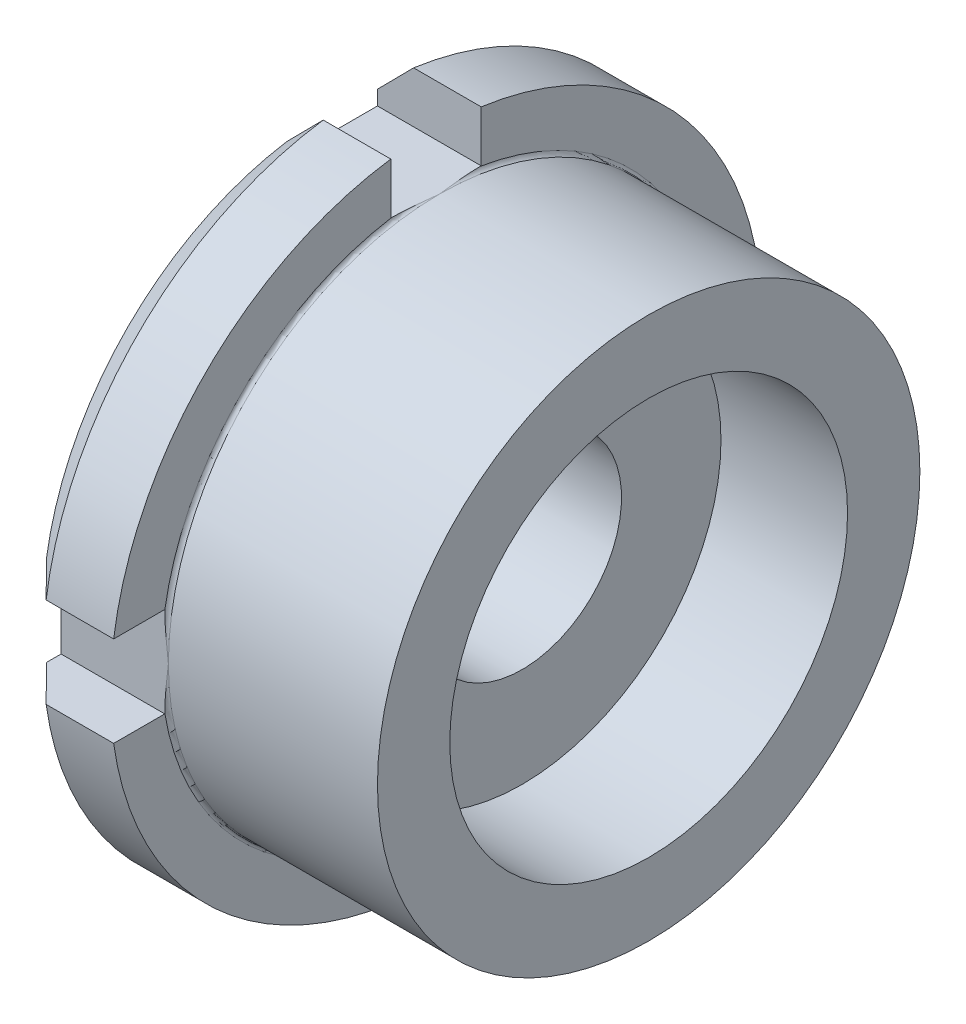
SolidWorks part; units mm, degrees
ref_plane "Front Plane" through (0, 0, 0) normal (0, 0, 1) x (1, 0, 0)
ref_plane "Top Plane" through (0, 0, 0) normal (0, 1, 0) x (1, 0, 0)
ref_plane "Right Plane" through (0, 0, 0) normal (1, 0, 0) x (0, 0, -1)
sketch "Sketch1" plane through (0, 0, 0) normal (0, 0, 1) x (1, 0, 0)
  line L0 (0, 0) -> (0, 5.5) construction
  line L1 (5.5, 5.5) -> (10.5, 5.5)
  line L2 (10.5, 5.5) -> (10.5, 11)
  line L3 (10.5, 11) -> (17.5, 11)
  line L4 (17.5, 11) -> (17.5, 15)
  line L5 (17.5, 15) -> (5.9357, 15)
  line L6 (5.7357, 15.2) -> (5.7357, 18)
  line L7 (5.7357, 18) -> (2, 18)
  line L8 (0, 16) -> (0, 12)
  line L9 (1, 11) -> (4.5, 11)
  line L10 (5.5, 10) -> (5.5, 5.5)
  line L11 (0, 16) -> (2, 18)
  line L12 (0, 0) -> (28.7428, 0) construction
  arc A0 (5.9357, 15) -> (5.7357, 15.2) centre (5.9357, 15.2) cw
  arc A1 (0, 12) -> (1, 11) centre (1, 12) ccw
  arc A2 (4.5, 11) -> (5.5, 10) centre (4.5, 10) cw
  point P19 (0, 11)
  point P22 (5.5, 11)
  dimension "D8" = 0.2
  dimension "D9" = 1
  dimension "D10" = 1
  dimension "D1" = 5.5
  dimension "D2" = 5.5
  dimension "D3" = 10.5
  dimension "D4" = 11
  dimension "D5" = 15
  dimension "D6" = 17.5
  dimension "D7" = 18
revolve "Revolve3" add sketch "Sketch1" angle 360 about L12
sketch "Sketch2" plane through (0, 0, 0) normal (-1, 0, 0) x (0, 0, 1)
  line L1 (2.5, 15) -> (2.5, 18)
  line L2 (-2.5, 15) -> (-2.5, 18)
  line L3 (-2.5, 15) -> (2.5, 15)
  line L7 (-2.5, 18) -> (2.5, 18)
  point P3 (2.5, 0)
  point P4 (2.5, 21.9264)
  point P5 (-2.5, 0)
  point P6 (-2.5, 21.9264)
  dimension "D1" = 5
  dimension "D2" = 3
extrude "Cut-Extrude1" cut sketch "Sketch2" against normal through all both and the other way through all
pattern_circular "CirPattern3" count 4 over 360 about axis through (0, 0, 0) along (-1, 0, 0) of "Cut-Extrude1"
scale "Scale1" scale about centroid uniform scaling yes scale factor 0.317565
